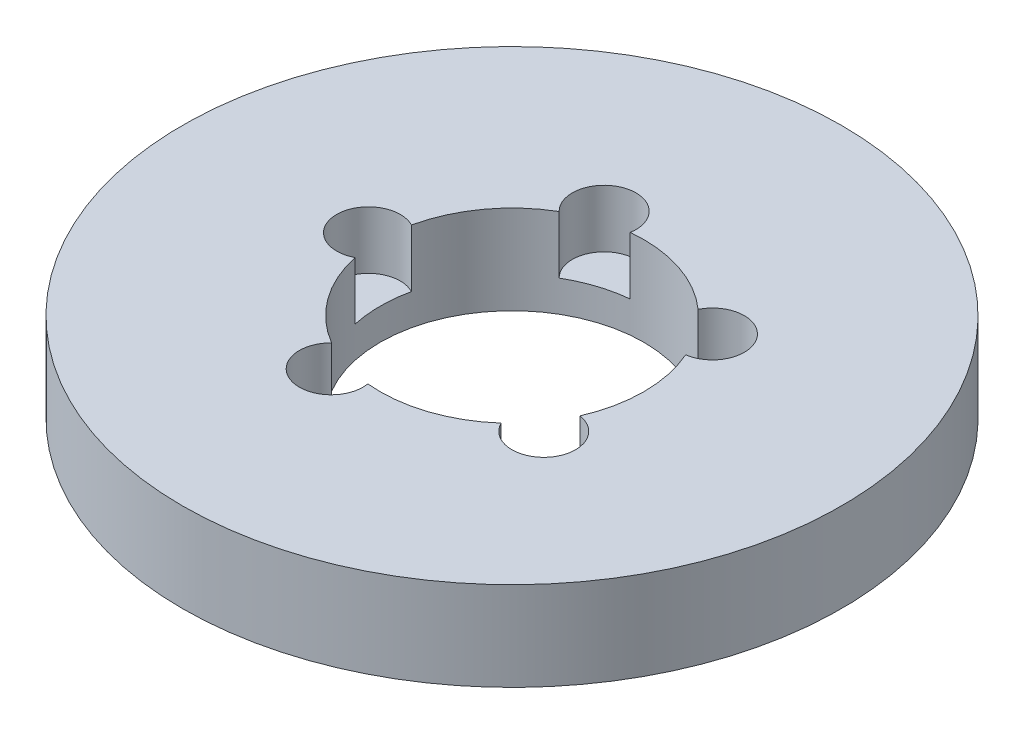
SolidWorks part; units mm, degrees
ref_plane "Front Plane" through (0, 0, 0) normal (0, 0, 1) x (1, 0, 0)
ref_plane "Top Plane" through (0, 0, 0) normal (0, 1, 0) x (1, 0, 0)
ref_plane "Right Plane" through (0, 0, 0) normal (1, 0, 0) x (0, 0, -1)
sketch "Sketch1" plane through (0, 0, 0) normal (0, 1, 0) x (1, 0, 0)
  circle A0 centre (0, 0) radius 100
  dimension "FLANGE_OD" = 200
extrude "Boss-Extrude1" add sketch "Sketch1" along normal blind 27
sketch "Sketch2" plane through (0, 0, 0) normal (0, 1, 0) x (1, 0, 0)
  circle A0 centre (0, 0) radius 40
  dimension "BORE_D" = 80
extrude "Cut-Extrude1" cut sketch "Sketch2" along normal through all
sketch "Sketch3" plane through (0, 27, 0) normal (0, 1, 0) x (1, 0, 0)
  circle A0 centre (0, 0) radius 43.5464 construction
  circle A1 centre (-43.5464, 0) radius 9.6591
  dimension "BOLT_D" = 19.3183
  dimension "BOLT_PCD" = 87.0928
extrude "Cut-Extrude2" cut sketch "Sketch3" against normal blind 17.4961
pattern_circular "CirPattern1" count 5 over 360 about axis through (0, 0, 0) along (0, 1, 0) of "Cut-Extrude2"
